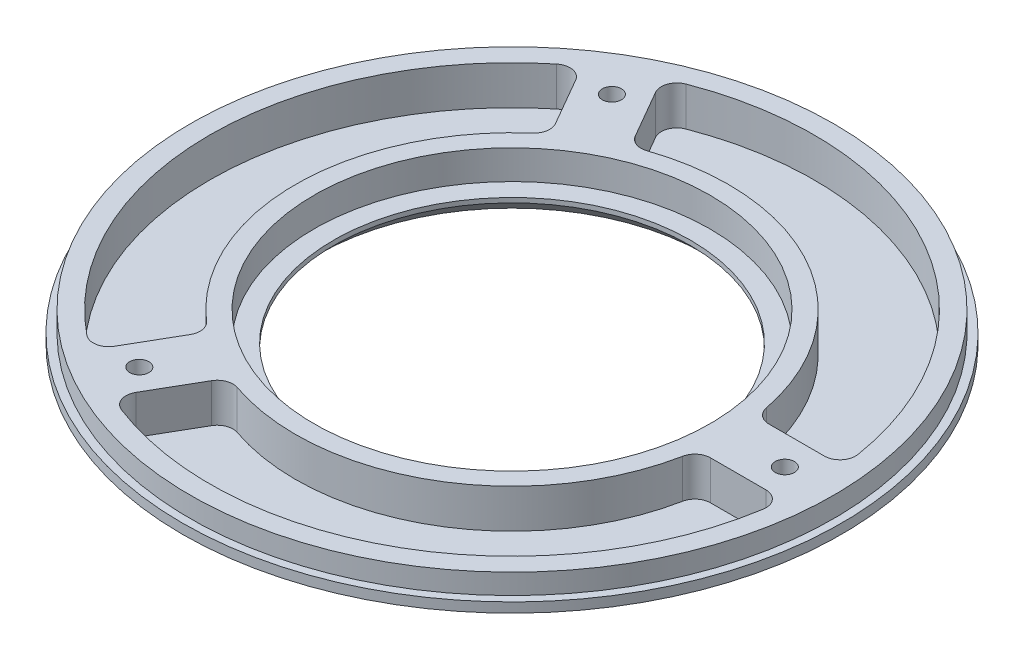
SolidWorks part; units mm, degrees
material "6061-T6 (SS)"
ref_plane "Front Plane" through (0, 0, 0) normal (0, 0, 1) x (1, 0, 0)
ref_plane "Top Plane" through (0, 0, 0) normal (0, 1, 0) x (1, 0, 0)
ref_plane "Right Plane" through (0, 0, 0) normal (1, 0, 0) x (0, 0, -1)
sketch "Sketch2" plane through (0, 0, 0) normal (1, 0, 0) x (0, 0, -1)
  line L0 (-45.8, 0) -> (-82.55, 0)
  line L1 (-82.55, 0) -> (-82.55, 12.7)
  line L2 (-82.55, 12.7) -> (-50.8, 12.7)
  line L3 (-45.8, 0) -> (-45.8, 5.2)
  line L4 (-45.8, 5.2) -> (-50.8, 5.2)
  line L5 (-50.8, 5.2) -> (-50.8, 12.7)
  line L6 (-80.2166, 12.7) -> (-80.2166, 0) construction
  dimension "D1" = 82.55
  dimension "D2" = 12.7
  dimension "D3" = 50.8
  dimension "D4" = 5
  dimension "D5" = 7.5
ref_axis "Axis1" through (0, -0.635, 0) along (0, 1, 0)
revolve "Revolve1" add sketch "Sketch2" angle 360 about axis through (0, -0.635, 0) along (0, 1, 0)
hole_wizard "#90 (0.0087) Diameter Hole1" positions "Sketch6" profile "Sketch7" hole size "#90" standard "ANSI Inch" end condition through all
sketch "Sketch6" plane through (0, 12.7, 0) normal (0, 1, 0) x (1, 0, 0)
  line L0 (0, 0) -> (-69.8201, 120.932) construction
  line L2 (0, 0) -> (0, 109.0908) construction
  point P0 (-35, 60.6218)
  dimension "D1" = 30
  dimension "D2" = 70
sketch "Sketch7" plane through (-35, 12.7, -60.6218) normal (1, 0, 0) x (0, 0, 1)
  line L0 (0, 0) -> (0, 12.7)
  line L1 (0, 12.7) -> (0.1105, 12.7)
  line L2 (0.1105, 12.7) -> (0.1105, 0)
  line L5 (0.1105, 0) -> (0, 0)
  line L11 (0, -6.35) -> (0, 107.95) construction
  dimension "Thru Hole Dia." = 0.221
  dimension "Thru Hole Depth" = 12.7
pattern_circular "CirPattern3" count 3 over 360 about axis through (0, -0.635, 0) along (0, 1, 0) of "#90 (0.0087) Diameter Hole1"
sketch "Sketch8" plane through (0, 12.7, 0) normal (0, 1, 0) x (1, 0, 0)
  line L4 (0, 0) -> (46.9997, 81.4059) construction
  line L5 (-21.0255, 51.4172) -> (-32.098, 70.5955)
  line L6 (55.0414, 7.5) -> (77.1865, 7.5)
  line L7 (0, 0) -> (-35, 60.6218) construction
  arc A0 (-21.0255, 51.4172) -> (55.0414, 7.5) centre (0, 0) cw
  arc A1 (-32.098, 70.5955) -> (77.1865, 7.5) centre (0, 0) cw
  circle A2 centre (0, 0) radius 82.55 construction
  dimension "D1" = 27
  dimension "D2" = 5
  dimension "D3" = 7.5
  dimension "D4" = 60
extrude "Cut-Extrude1" cut sketch "Sketch8" against normal blind 10
fillet "Fillet1" radius 4 4 edges at (-21.0255, 7.7, -51.4172) (55.0414, 7.7, -7.5) (77.1865, 7.7, -7.5) (-32.098, 7.7, -70.5955)
pattern_circular "CirPattern4" count 3 over 360 about axis through (0, -0.635, 0) along (0, 1, 0) of "Cut-Extrude1", "Fillet1"
chamfer "Chamfer1" distance 4 angle 45 1 edges at (0, 0, -45.8)
sketch "Sketch10" plane through (0, 0, 0) normal (0, -1, 0) x (1, 0, 0)
  circle A0 centre (0, 0) radius 82.55
  circle A1 centre (0, 0) radius 84.55
  circle A2 centre (0, 0) radius 82.55 construction
  dimension "D1" = 2
extrude "Boss-Extrude1" add sketch "Sketch10" against normal blind 7.5
chamfer "Chamfer3" distance 5 angle 60 1 edges at (0, 0, -84.55) first distance on face at (0, 7.5, -84.55)
fillet "Fillet4" radius 5 1 edges at (0, 0, 75.8897)
hole_wizard "CBORE for #10 Binding Head Machine Screw1" positions "Sketch13" profile "Sketch14" counterbore size "#10" standard "ANSI Inch" end condition through all
sketch "Sketch13" plane through (0, 0, 0) normal (0, -1, 0) x (-1, 0, 0)
  point P4 (35, 60.6218)
sketch "Sketch14" plane through (-35, 0, -60.6218) normal (1, 0, 0) x (0, 0, -1)
  line L0 (0, 0) -> (0, 12.7)
  line L1 (0, 12.7) -> (2.4574, 12.7)
  line L3 (2.4574, 12.7) -> (2.4575, 2.794)
  line L4 (2.4575, 2.794) -> (4.7625, 2.794)
  line L5 (4.7625, 2.794) -> (4.7625, 0)
  line L7 (4.7625, 0) -> (0, 0)
  line L11 (0, -6.35) -> (0, 107.95) construction
  dimension "Thru Hole Dia." = 4.9149
  dimension "Thru Hole Depth" = 12.7
  dimension "C'Bore Dia." = 9.525
  dimension "C'Bore Depth" = 2.794
pattern_circular "CirPattern5" count 3 over 360 about axis through (0, -0.635, 0) along (0, 1, 0) of "CBORE for #10 Binding Head Machine Screw1"
equation "\"TubeDiameter\" = 6.500in"
